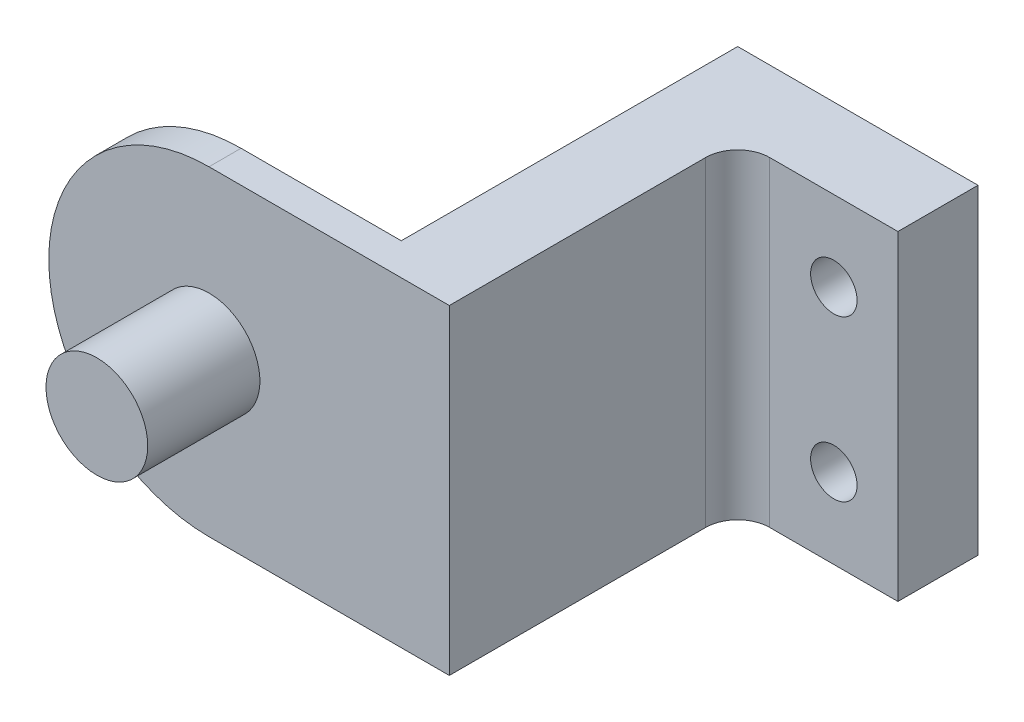
SolidWorks part; units mm, degrees
material "ABS"
ref_plane "Front" through (0, 0, 0) normal (0, 0, 1) x (1, 0, 0)
ref_plane "Top" through (0, 0, 0) normal (0, 1, 0) x (1, 0, 0)
ref_plane "Right" through (0, 0, 0) normal (1, 0, 0) x (0, 0, -1)
sketch "Esquisse1" plane through (0, 0, 0) normal (0, 0, 1) x (1, 0, 0)
  line L1 (-2.5, 10) -> (2.5, 10)
  line L2 (-2.5, 10) -> (-2.5, -10)
  line L3 (-2.5, -10) -> (2.5, -10)
  line L4 (2.5, 10) -> (2.5, -10)
  line L5 (-2.5, 10) -> (2.5, -10) construction
  line L6 (-2.5, -10) -> (2.5, 10) construction
  point P0 (0, 0)
  dimension "D1" = 5
  dimension "D2" = 20
extrude "Boss.-Extru.1" add sketch "Esquisse1" along normal blind 21
sketch "Esquisse2" plane through (0, 0, 21) normal (0, 0, 1) x (1, 0, 0)
  line L0 (-2.5, -10) -> (2.5, -10) construction
  line L1 (2.5, 10) -> (-22.5, 10)
  line L2 (2.5, 10) -> (2.5, -10)
  line L3 (2.5, -10) -> (-22.5, -10)
  line L4 (-22.5, 10) -> (-22.5, -10)
  dimension "D1" = 25
extrude "Boss.-Extru.2" add sketch "Esquisse2" along normal blind 2
fillet "Congé1" radius 10 2 edges at (-22.5, 10, 22) (-22.5, -10, 22)
sketch "Esquisse3" plane through (0, 0, 23) normal (0, 0, 1) x (1, 0, 0)
  circle A0 centre (-12.5, 0) radius 3.175
  arc A1 (-12.5, 10) -> (-22.5, 0) centre (-12.5, 0) ccw construction
  point P2 (0, 0)
  point P3 (0, 0)
  dimension "D1" = 6.35
extrude "Boss.-Extru.3" add sketch "Esquisse3" along normal blind 7
sketch "Esquisse5" plane through (2.5, 0, 0) normal (1, 0, 0) x (0, 0, -1)
  line L0 (-23, -10) -> (0, -10) construction
  line L1 (0, 10) -> (-5, 10)
  line L2 (0, 10) -> (0, -10)
  line L3 (0, -10) -> (-5, -10)
  line L4 (-5, 10) -> (-5, -10)
  dimension "D1" = 5
extrude "Boss.-Extru.4" add sketch "Esquisse5" along normal blind 10
fillet "Congé2" radius 2 1 edges at (2.5, 0, 5)
sketch "Esquisse6" plane through (0, 0, 5) normal (0, 0, 1) x (1, 0, 0)
  line L0 (12.5, 10) -> (4.5, 10) construction
  line L1 (12.5, 10) -> (12.5, -10) construction
  circle A0 centre (8.5, 5) radius 1.45
  circle A1 centre (8.5, -5) radius 1.45
  dimension "D1" = 2.9
  dimension "D2" = 10
  dimension "D3" = 5
  dimension "D4" = 4
extrude "Enlèv. mat.-Extru.1" cut sketch "Esquisse6" against normal up to next
